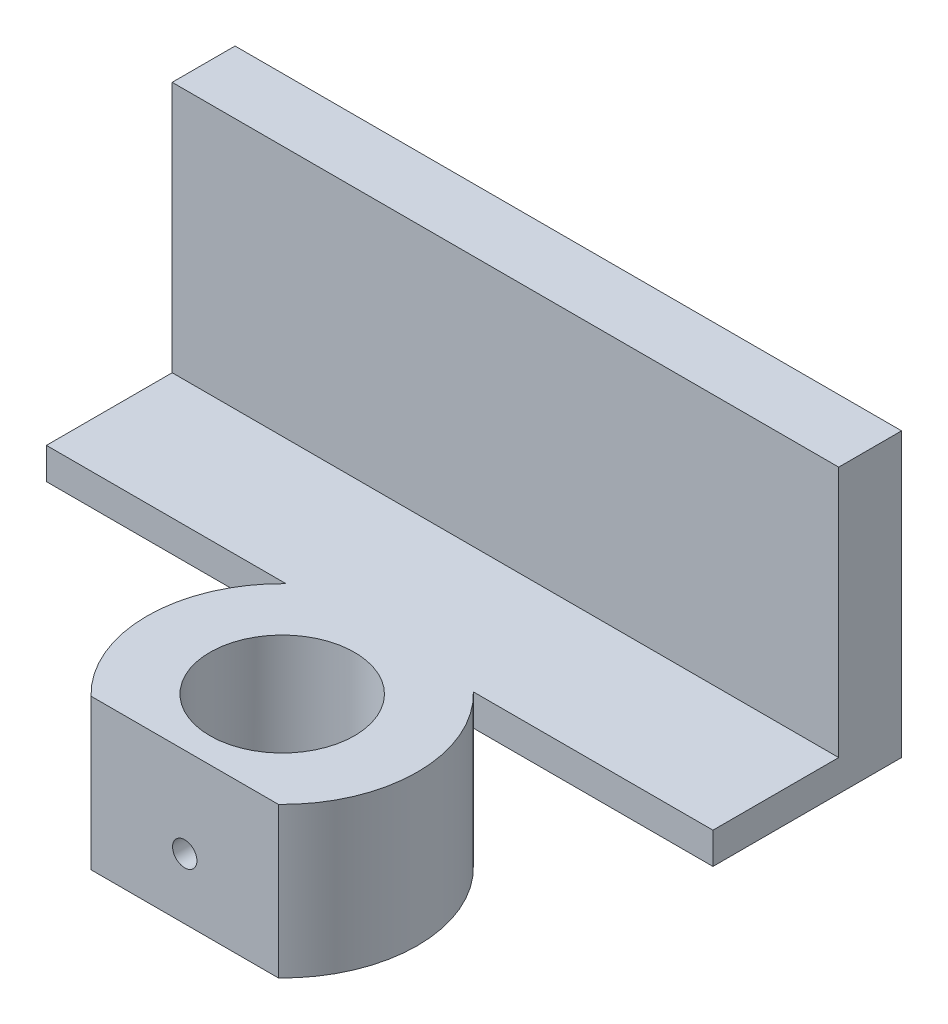
SolidWorks part; units mm, degrees
ref_plane "前基準面" through (0, 0, 0) normal (0, 0, 1) x (1, 0, 0)
ref_plane "上基準面" through (0, 0, 0) normal (0, 1, 0) x (1, 0, 0)
ref_plane "右基準面" through (0, 0, 0) normal (1, 0, 0) x (0, 0, -1)
sketch "草圖1" plane through (0, 0, 0) normal (0, 0, 1) x (1, 0, 0)
  line L0 (0, 0) -> (0, 60)
  line L1 (0, 60) -> (30.6281, 60)
  line L2 (30.6281, 60) -> (78.9616, 54.8725)
  line L3 (280.2175, 30) -> (280.2175, 0)
  line L4 (280.2175, 0) -> (227.8434, 0)
  line L5 (153.3118, -9.6901) -> (107.7898, -9.6901)
  spline S0 degree 3 poles (78.9616, 54.8725) (112.2329, 21.4354) (171.3693, 45.9237) (246.5881, 58.3745) (280.2175, 30) knots 0 0 0 0 0.429026 1 1 1 1
  spline S1 degree 1 poles (227.8434, 0) (153.3118, -9.6901) knots 0 0 1 1
  spline S2 degree 1 poles (107.7898, -9.6901) (0, 0) knots 0 0 1 1
  dimension "D1" = 30
  dimension "D2" = 60
extrude "填料-伸長1" add sketch "草圖1" along normal blind 31
fillet "圓角3" radius 10 9 edges at (0, 30, 31) (15.3141, 60, 31) (54.7949, 57.4363, 31) (280.2175, 15, 31) (254.0304, 0, 31) (130.5508, -9.6901, 31)
fillet "圓角4" radius 10 9 edges at (130.5508, -9.6901, 0) (254.0304, 0, 0) (280.2175, 15, 0) (54.7949, 57.4363, 0) (15.3141, 60, 0) (0, 30, 0)
ref_plane "平面1" through (0, -11, 0) normal (0, 1, 0) x (1, 0, 0)
ref_plane "平面2" through (0, 0, 0) normal (1, 0, 0) x (0, 0, -1)
sketch "草圖31" plane through (0, 0, 0) normal (0, 0, -1) x (-1, 0, 0)
  line L0 (75.0986, -11) -> (-75.0986, -11) construction
  line L1 (0, -11) -> (-31.7159, -11)
  line L2 (0, -11) -> (0, 70.0151)
  line L3 (0, 70.0151) -> (-31.7159, 70.0151)
  line L4 (-31.7159, -11) -> (-31.7159, 70.0151)
  line L5 (0, 13.1504) -> (0, -13.1504) construction
extrude "除料-伸長20" cut sketch "草圖31" against normal blind 97
sketch "草圖38" plane through (0, -11, 0) normal (0, 1, 0) x (1, 0, 0)
  line L0 (69.7528, -1010) -> (69.7528, 48990) construction
  line L1 (31.7159, -10) -> (107.7898, -10) construction
  line L2 (-968.2841, -15.5) -> (49031.7159, -15.5) construction
  line L3 (31.7159, -21) -> (31.7159, -10) construction
  line L5 (52.2528, -8) -> (87.2528, -8)
  line L6 (52.2528, -8) -> (52.2528, -23)
  line L7 (52.2528, -23) -> (87.2528, -23)
  line L8 (87.2528, -8) -> (87.2528, -23)
  line L9 (52.2528, -8) -> (87.2528, -23) construction
  line L10 (52.2528, -23) -> (87.2528, -8) construction
  point P5 (69.7528, -10)
  point P6 (69.7528, -15.5)
  point P10 (31.7159, -15.5)
  dimension "D1" = 15
  dimension "D2" = 35
extrude "除料-伸長23" cut sketch "草圖38" along normal blind 37
sketch "草圖63" plane through (0, 0, 31) normal (0, 0, 1) x (1, 0, 0)
  line L0 (75.0986, -11) -> (-75.0986, -11) construction
  line L1 (192.2521, -11) -> (27.8442, -11)
  line L2 (192.2521, -11) -> (192.2521, 0)
  line L3 (192.2521, 0) -> (27.8442, 0)
  line L4 (27.8442, -11) -> (27.8442, 0)
extrude "除料-伸長34" cut sketch "草圖63" against normal blind 76
sketch "草圖65" plane through (0, 0, 31) normal (0, 0, 1) x (1, 0, 0)
  line L0 (31.7159, 7.1891) -> (31.7159, 0) construction
  line L1 (186.8562, -3.523) -> (31.7159, -3.523)
  line L2 (186.8562, -3.523) -> (186.8562, 2.472)
  line L3 (186.8562, 2.472) -> (31.7159, 2.472)
  line L4 (31.7159, -3.523) -> (31.7159, 2.472)
extrude "除料-伸長35" cut sketch "草圖65" against normal blind 76
sketch "草圖67" plane through (0, 0, 31) normal (0, 0, 1) x (1, 0, 0)
  line L0 (31.7159, 13.6752) -> (31.7159, 2.472)
  line L1 (31.7159, 49.8285) -> (31.7159, 7.1891) construction
  line L2 (31.7159, 2.472) -> (43.0787, 2.472)
  line L3 (31.7159, 2.472) -> (84.1879, 2.472) construction
  line L4 (43.0787, 2.472) -> (31.7159, 13.6752)
extrude "除料-伸長36" cut sketch "草圖67" against normal blind 76
fillet "圓角10" radius 21 1 edges at (43.0787, 2.472, 15.5)
fillet "圓角11" radius 21 1 edges at (31.7159, 13.6752, 15.5)
sketch "草圖69" plane through (0, -11, 0) normal (0, 1, 0) x (1, 0, 0)
  line L1 (52.2528, -8) -> (42.2528, -8)
  line L2 (52.2528, -8) -> (52.2528, -23)
  line L3 (52.2528, -23) -> (42.2528, -23)
  line L4 (42.2528, -8) -> (42.2528, -23)
  dimension "D1" = 10
extrude "除料-伸長37" cut sketch "草圖69" along normal blind 42
sketch "草圖72" plane through (0, 0, 31) normal (0, 0, 1) x (1, 0, 0)
  line L1 (31.7159, 59.8846) -> (78.9616, 59.8846)
  line L2 (31.7159, 59.8846) -> (31.7159, 54.8725)
  line L3 (31.7159, 54.8725) -> (78.9616, 54.8725)
  line L4 (78.9616, 59.8846) -> (78.9616, 54.8725)
extrude "除料-伸長39" cut sketch "草圖72" against normal blind 42
ref_plane "平面3" through (0, 0, 32) normal (0, 0, 1) x (1, 0, 0)
sketch "草圖75" plane through (0, -11, 0) normal (0, 1, 0) x (1, 0, 0)
  line L0 (-963.0535, -15.5) -> (49036.9465, -15.5) construction
  line L1 (36.9465, 0) -> (36.9465, -31) construction
  circle A0 centre (98.9056, -15.5) radius 11.5
  point P5 (36.9465, -15.5)
  dimension "D1" = 23
extrude "伸長-薄件1" add sketch "草圖75" along normal blind 21 and the other way blind 20 thin thin type one direction wall 10
sketch "草圖76" plane through (0, 10, 0) normal (0, 1, 0) x (1, 0, 0)
  line L1 (113.8053, 0) -> (81.7542, 0)
  line L2 (113.8053, 0) -> (113.8053, 14.7116)
  line L3 (113.8053, 14.7116) -> (81.7542, 14.7116)
  line L4 (81.7542, 0) -> (81.7542, 14.7116)
extrude "除料-伸長41" cut sketch "草圖76" against normal through all
sketch "草圖77" plane through (0, 10, 0) normal (0, 1, 0) x (1, 0, 0)
  line L1 (84.006, -31) -> (136.8048, -31)
  line L2 (84.006, -31) -> (84.006, -39)
  line L3 (84.006, -39) -> (136.8048, -39)
  line L4 (136.8048, -31) -> (136.8048, -39)
  dimension "D1" = 8
extrude "除料-伸長42" cut sketch "草圖77" against normal through all
sketch "草圖78" plane through (0, 0, 0) normal (0, 0, -1) x (-1, 0, 0)
  line L0 (-1084.006, -14.2558) -> (48915.994, -14.2558) construction
  line L1 (-84.006, -31) -> (-84.006, 2.4884) construction
  line L2 (-98.9056, -1031) -> (-98.9056, 48969) construction
  line L3 (-84.006, -31) -> (-113.8053, -31) construction
  circle A0 centre (-98.9056, -14.2558) radius 1.935
  point P5 (-84.006, -14.2558)
  point P10 (-98.9056, -31)
  dimension "D1" = 3.87
extrude "除料-伸長43" cut sketch "草圖78" against normal blind 38
sketch "草圖82" plane through (0, -11, 0) normal (0, 1, 0) x (1, 0, 0)
  circle A0 centre (98.9056, -15.5) radius 11.5
extrude "除料-伸長46" cut sketch "草圖82" along normal blind 37
sketch "草圖87" plane through (0, 0, 0) normal (1, 0, 0) x (0, 0, -1)
  line L0 (0, -31) -> (0, 2.4884) construction
  line L1 (-43.154, -35.5812) -> (0, -35.5812)
  line L2 (-43.154, -35.5812) -> (-43.154, -23.9099)
  line L3 (-43.154, -23.9099) -> (0, -23.9099)
  line L4 (0, -35.5812) -> (0, -23.9099)
extrude "除料-伸長51" cut sketch "草圖87" along normal blind 160
sketch "草圖92" plane through (0, 0, 31) normal (0, 0, 1) x (1, 0, 0)
  line L1 (193.5677, 0) -> (25.7499, 0)
  line L2 (193.5677, 0) -> (193.5677, 60.1529)
  line L3 (193.5677, 60.1529) -> (25.7499, 60.1529)
  line L4 (25.7499, 0) -> (25.7499, 60.1529)
extrude "除料-伸長54" cut sketch "草圖92" against normal blind 60 and the other way blind 60
sketch "草圖93" plane through (0, 0, 31) normal (0, 0, 1) x (1, 0, 0)
  line L1 (332.5823, -35.9286) -> (171.2206, -35.9286)
  line L2 (332.5823, -35.9286) -> (332.5823, 75.116)
  line L3 (332.5823, 75.116) -> (171.2206, 75.116)
  line L4 (171.2206, -35.9286) -> (171.2206, 75.116)
extrude "除料-伸長55" cut sketch "草圖93" against normal blind 35
sketch "草圖94" plane through (0, 0, 0) normal (0, 0, -1) x (-1, 0, 0)
  line L0 (-113.8053, -23.9099) -> (-113.8053, 0) construction
  line L1 (-84.006, 0) -> (-113.8053, 0)
  line L2 (-84.006, 0) -> (-84.006, -5)
  line L3 (-84.006, -5) -> (-113.8053, -5)
  line L4 (-113.8053, 0) -> (-113.8053, -5)
  dimension "D1" = 5
extrude "填料-伸長2" add sketch "草圖94" along normal blind 50
sketch "草圖96" plane through (84.006, 0, 0) normal (-1, 0, 0) x (0, 0, 1)
  line L1 (0, -5) -> (-50, -5)
  line L2 (0, -5) -> (0, 0)
  line L3 (0, 0) -> (-50, 0)
  line L4 (-50, -5) -> (-50, 0)
extrude "填料-伸長3" add sketch "草圖96" along normal blind 38.1
sketch "草圖97" plane through (113.8053, 0, 0) normal (1, 0, 0) x (0, 0, -1)
  line L1 (50, -5) -> (0, -5)
  line L2 (50, -5) -> (50, 0)
  line L3 (50, 0) -> (0, 0)
  line L4 (0, -5) -> (0, 0)
extrude "填料-伸長4" add sketch "草圖97" along normal blind 38.1
sketch "草圖98" plane through (0, -5, 0) normal (0, -1, 0) x (1, 0, 0)
  line L0 (45.906, 0) -> (45.906, -30) construction
  line L1 (45.906, -50) -> (45.906, 0) construction
  line L3 (45.906, -30) -> (151.9053, -30)
  line L4 (45.906, -30) -> (45.906, -50)
  line L5 (45.906, -50) -> (151.9053, -50)
  line L6 (151.9053, -30) -> (151.9053, -50)
  dimension "D1" = 30
extrude "除料-伸長56" cut sketch "草圖98" against normal blind 38.1
sketch "草圖99" plane through (0, 0, 0) normal (0, 1, 0) x (1, 0, 0)
  line L0 (151.9053, 30) -> (151.9053, 0) construction
  line L1 (45.906, 30) -> (151.9053, 30)
  line L2 (45.906, 30) -> (45.906, 20)
  line L3 (45.906, 20) -> (151.9053, 20)
  line L4 (151.9053, 30) -> (151.9053, 20)
  dimension "D1" = 10
extrude "填料-伸長5" add sketch "草圖99" along normal blind 40
sketch "草圖101" plane through (0, -5, 0) normal (0, -1, 0) x (1, 0, 0)
  line L0 (45.906, -24.7213) -> (55.906, -24.7213) construction
  line L1 (45.906, -30) -> (45.906, 0) construction
  line L2 (151.9053, -24.7213) -> (141.9053, -24.7213) construction
  line L3 (151.9053, 0) -> (151.9053, -30) construction
  line L5 (53.406, -22.2213) -> (58.406, -22.2213)
  line L6 (53.406, -22.2213) -> (53.406, -27.2213)
  line L7 (53.406, -27.2213) -> (58.406, -27.2213)
  line L8 (58.406, -22.2213) -> (58.406, -27.2213)
  line L9 (53.406, -22.2213) -> (58.406, -27.2213) construction
  line L10 (53.406, -27.2213) -> (58.406, -22.2213) construction
  line L11 (139.4053, -22.2213) -> (144.4053, -22.2213)
  line L12 (139.4053, -22.2213) -> (139.4053, -27.2213)
  line L13 (139.4053, -27.2213) -> (144.4053, -27.2213)
  line L14 (144.4053, -22.2213) -> (144.4053, -27.2213)
  line L15 (139.4053, -22.2213) -> (144.4053, -27.2213) construction
  line L16 (139.4053, -27.2213) -> (144.4053, -22.2213) construction
  dimension "D1" = 10
  dimension "D2" = 10
  dimension "D3" = 5
  dimension "D4" = 5
  dimension "D5" = 5
  dimension "D6" = 5
extrude "除料-伸長57" cut sketch "草圖101" against normal blind 40
sketch "草圖104" plane through (0, 35, 0) normal (0, -1, 0) x (1, 0, 0)
  line L0 (55.906, -1027.2213) -> (55.906, 48972.7787) construction
  line L1 (53.406, -27.2213) -> (58.406, -27.2213) construction
  line L2 (53.406, -27.2213) -> (58.406, -27.2213) construction
  line L3 (56.9045, -30.5669) -> (54.9074, -30.5669)
  line L4 (56.9045, -30.5669) -> (56.9045, -27.2213)
  line L5 (56.9045, -27.2213) -> (54.9074, -27.2213)
  line L6 (54.9074, -30.5669) -> (54.9074, -27.2213)
  line L7 (56.9045, -30.5669) -> (54.9074, -27.2213) construction
  line L8 (56.9045, -27.2213) -> (54.9074, -30.5669) construction
  point P1 (55.906, -28.8941)
  point P5 (55.906, -27.2213)
  dimension "D1" = 1.9971
extrude "除料-伸長59" cut sketch "草圖104" along normal blind 40
sketch "草圖105" plane through (0, -5, 0) normal (0, -1, 0) x (1, 0, 0)
  line L0 (141.9053, -1022.2213) -> (141.9053, 48977.7787) construction
  line L1 (144.4053, -22.2213) -> (139.4053, -22.2213) construction
  line L2 (151.9053, -30) -> (56.9045, -30) construction
  line L3 (140.9053, -32.7787) -> (142.9053, -32.7787)
  line L4 (140.9053, -32.7787) -> (140.9053, -27.2213)
  line L5 (140.9053, -27.2213) -> (142.9053, -27.2213)
  line L6 (142.9053, -32.7787) -> (142.9053, -27.2213)
  line L7 (140.9053, -32.7787) -> (142.9053, -27.2213) construction
  line L8 (140.9053, -27.2213) -> (142.9053, -32.7787) construction
  line L9 (139.4053, -27.2213) -> (144.4053, -27.2213) construction
  point P1 (141.9053, -30)
  point P5 (141.9053, -22.2213)
  dimension "D1" = 2
extrude "除料-伸長60" cut sketch "草圖105" against normal blind 40
